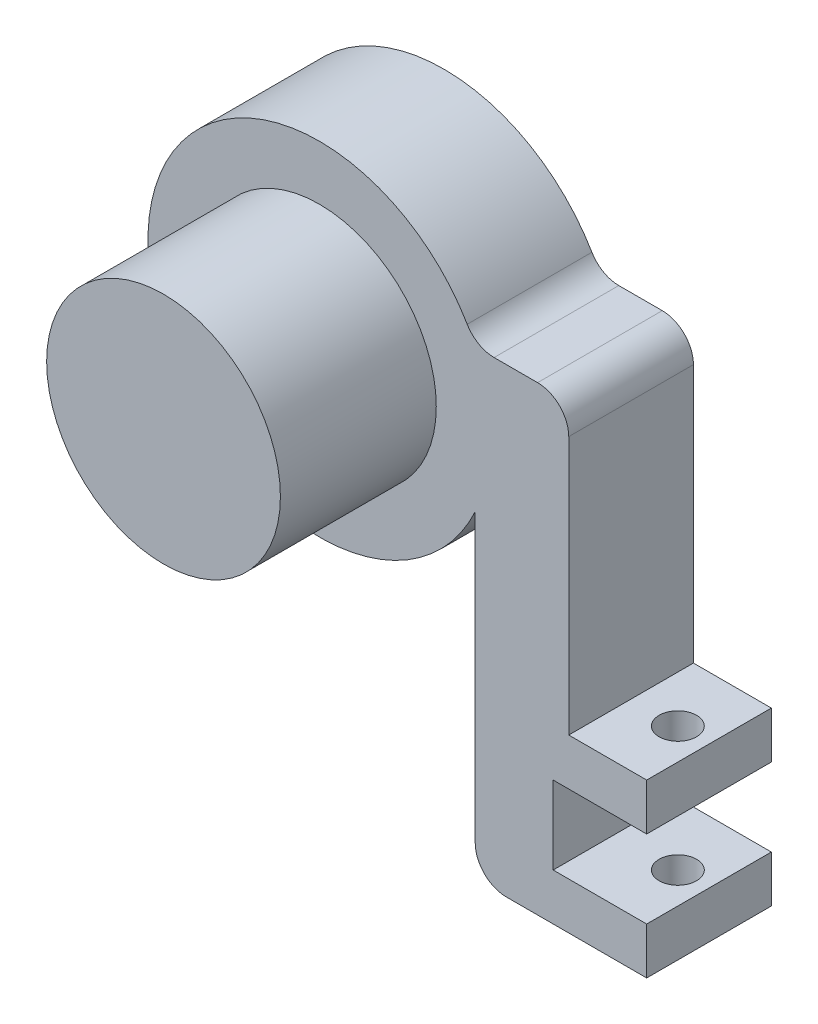
SolidWorks part; units mm, degrees
ref_plane "Plan de face" through (0, 0, 0) normal (0, 0, 1) x (1, 0, 0)
ref_plane "Plan de dessus" through (0, 0, 0) normal (0, 1, 0) x (1, 0, 0)
ref_plane "Plan de droite" through (0, 0, 0) normal (1, 0, 0) x (0, 0, -1)
sketch "Esquisse1" plane through (0, 0, 0) normal (0, 0, 1) x (1, 0, 0)
  line L1 (0, 0) -> (32, 0) construction
  line L2 (0, 0) -> (0, -36) construction
  line L3 (0, -36) -> (32, -36) construction
  line L4 (32, 0) -> (32, -36) construction
  line L5 (21, -6.4174) -> (27, -6.4174)
  line L7 (27, -6.4174) -> (27, -25)
  line L8 (32, -28) -> (32, -25)
  line L9 (32, -36) -> (21, -36)
  line L10 (32, -36) -> (32, -33)
  line L11 (32, -25) -> (27, -25)
  line L14 (21, -36) -> (21, -15.5826)
  line L17 (32, -33) -> (26, -33)
  line L19 (32, -28) -> (26, -28)
  line L20 (26, -33) -> (26, -28)
  line L21 (21, -6.4174) -> (21, -15.5826) construction
  arc A0 (21, -6.4174) -> (21, -15.5826) centre (11, -11) ccw
  point P6 (21, -11)
  point P7 (20.0394, -13.5)
  point P11 (20.0394, -14.8266)
  point P20 (26, -30.5)
  dimension "D3" = 22
  dimension "D1" = 32
  dimension "D2" = 36
  dimension "D4" = 11
  dimension "D5" = 11
  dimension "D6" = 11
  dimension "D8" = 6
  dimension "D9" = 5
  dimension "D10" = 5.5
  dimension "D11" = 5
  dimension "D7" = 21
extrude "Boss.-Extru.1" add sketch "Esquisse1" along normal blind 8
sketch "Esquisse2" plane through (0, -25, 0) normal (0, 1, 0) x (1, 0, 0)
  line L0 (27, -8) -> (27, 0) construction
  line L1 (32, -8) -> (27, -8) construction
  circle A0 centre (30, -4) radius 1
  dimension "D1" = 2
  dimension "D2" = 3
  dimension "D3" = 4
extrude "Enlèv. mat.-Extru.1" cut sketch "Esquisse2" against normal up to surface (11 mm away) up to face at (26.5, -36, 4)
hole_wizard "Dégagement M21" positions "Esquisse3" profile "Esquisse4" hole size "M2" standard "ISO"
sketch "Esquisse3" plane through (0, -25, 0) normal (0, 1, 0) x (1, 0, 0)
  point P0 (30, -4)
sketch "Esquisse4" plane through (30, -25, 4) normal (1, 0, 0) x (0, 0, 1)
  line L0 (0, 0) -> (0, 11.721)
  line L1 (0, 11.721) -> (1.2, 11)
  line L2 (1.2, 11) -> (1.2, 0)
  line L5 (1.2, 0) -> (0, 0)
  line L10 (0, 11.721) -> (-1.2, 11) construction
  line L11 (0, -6.35) -> (0, 107.95) construction
  dimension "Diamètre du perçage" = 2.4
  dimension "Profondeur du perçage" = 11
  dimension "Angle de pointe" = 118
fillet "Congé1" radius 2 3 edges at (21, -36, 4) (21, -6.4174, 4) (27, -6.4174, 4)
sketch "Esquisse5" plane through (0, 0, 8) normal (0, 0, 1) x (1, 0, 0)
  circle A0 centre (11, -11) radius 7.5
  dimension "D1" = 15
extrude "Boss.-Extru.2" add sketch "Esquisse5" along normal blind 10
equation "\"D4@Esquisse1\"=\"D3@Esquisse1\"/2"
equation "\"D5@Esquisse1\"=\"D3@Esquisse1\"/2"
equation "\"D10@Esquisse1\"=\"D6@Esquisse1\"/2"
